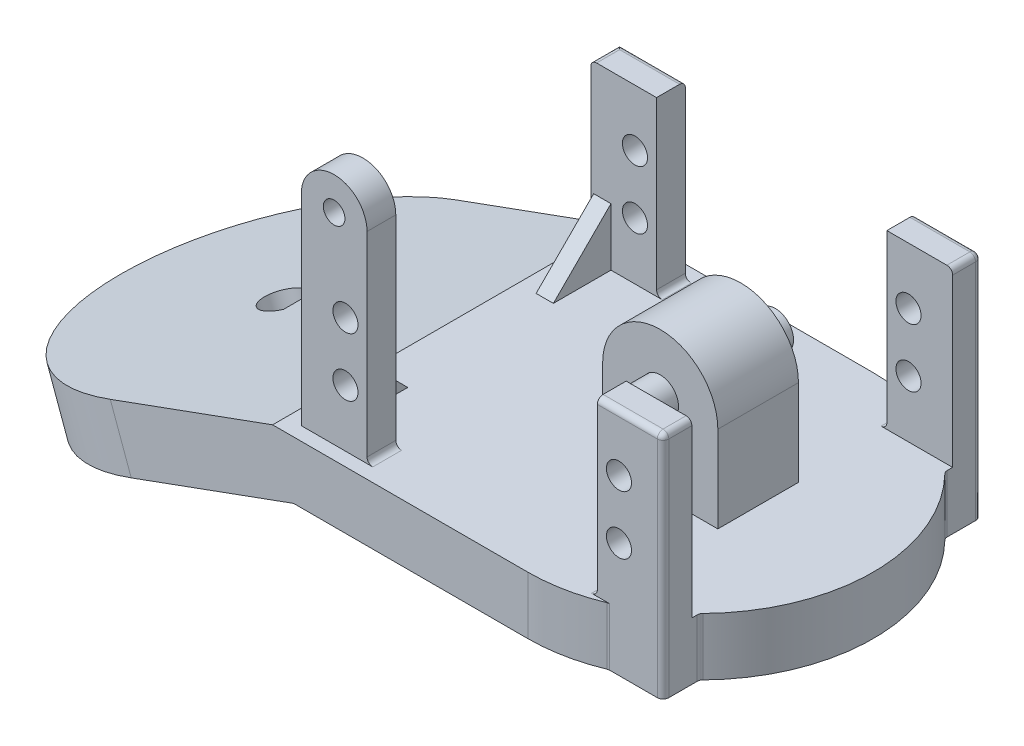
SolidWorks part; units mm, degrees
ref_plane "Plan de face" through (0, 0, 0) normal (0, 0, 1) x (1, 0, 0)
ref_plane "Plan de dessus" through (0, 0, 0) normal (0, 1, 0) x (1, 0, 0)
ref_plane "Plan de droite" through (0, 0, 0) normal (1, 0, 0) x (0, 0, -1)
sketch "Esquisse5" plane through (0, 0, 0) normal (0, 1, 0) x (1, 0, 0)
  line L0 (42.5, 0) -> (-42.5, 0) construction
  line L1 (42.5, -30) -> (-42.5, -30)
  line L2 (42.5, 30) -> (-42.5, 30)
  arc A0 (42.5, -30) -> (42.5, 30) centre (42.5, 0) ccw
  arc A1 (-42.5, 30) -> (-42.5, -30) centre (-42.5, 0) ccw
  point P2 (0, 0)
  dimension "D2" = 30
  dimension "D1" = 85
extrude "Boss.-Extru.3" add sketch "Esquisse5" along normal mid plane 10
sketch "Esquisse36" plane through (0, 0, 0) normal (0, 0, 1) x (1, 0, 0)
  line L0 (0, 0) -> (9.0993, -25)
  line L1 (9.0993, -25) -> (-112.5, -25)
  line L2 (-112.5, -25) -> (-112.5, 35)
  line L3 (-112.5, 35) -> (-12.739, 35)
  line L4 (-12.739, 35) -> (0, 0)
  line L5 (42.5, -5) -> (-42.5, -5) construction
  line L6 (42.5, 5) -> (-42.5, 5) construction
  line L7 (-42.5, 5) -> (-42.5, -5) construction
  dimension "D1" = 180
  dimension "D2" = 20
  dimension "D3" = 70
  dimension "D4" = 30
  dimension "D5" = 70
sketch "Esquisse7" plane through (0, 0, 0) normal (0, 0, 1) x (1, 0, 0)
  line L0 (42.5, 5) -> (32.5, 5)
  line L1 (-42.5, 5) -> (42.5, 5) construction
  line L2 (32.5, 5) -> (32.5, 20)
  line L3 (32.5, 20) -> (52.5, 20)
  line L4 (52.5, 20) -> (52.5, 5)
  line L5 (72.5, 5) -> (42.5, 5) construction
  line L6 (52.5, 5) -> (42.5, 5)
  arc A0 (32.5, 20) -> (52.5, 20) centre (42.5, 20) cw
  circle A1 centre (42.5, 20) radius 3.175
  dimension "D1" = 10
  dimension "D3" = 6.35
  dimension "D2" = 15
extrude "Boss.-Extru.5" add sketch "Esquisse7" along normal mid plane 14 contours A1 L3 A0 | A1 L3 L2 L0 L6 L4 region at (42.5, 12.1572, 0) region at (42.5, 24.5689, 0)
sketch "Esquisse10" plane through (0, -5, 0) normal (0, -1, 0) x (1, 0, 0)
  point P0 (42.5, 0)
ref_plane "Plan1" through (0, 0, 22.64) normal (0, 0, 1) x (1, 0, 0)
sketch "Esquisse13" plane through (0, 0, 22.64) normal (0, 0, 1) x (1, 0, 0)
  line L0 (-42.5, 5) -> (42.5, 5) construction
  line L1 (5.8, 5) -> (58.63, 5)
  line L2 (5.8, 5) -> (5.8, 29.91) construction
  line L3 (5.8, 29.91) -> (58.63, 29.91) construction
  line L4 (58.63, 5) -> (58.63, 29.91) construction
  line L5 (5.8, 5) -> (0.8, 5)
  line L6 (0.8, 5) -> (0.8, 34.91)
  line L7 (0.8, 34.91) -> (63.63, 34.91)
  line L8 (63.63, 34.91) -> (63.63, 5)
  line L9 (63.63, 5) -> (58.63, 5)
  line L10 (63.63, 5) -> (58.63, 5)
  line L11 (0.8, 5) -> (5.8, 5)
  line L12 (12.215, 5) -> (12.215, 29.91)
  line L13 (12.215, 29.91) -> (52.215, 29.91)
  line L14 (52.215, 29.91) -> (52.215, 5)
  line L15 (52.215, 5) -> (12.215, 5)
  circle A0 centre (42.5, 20) radius 3.175 construction
  circle A2 centre (55.97, 25.08) radius 2.18
  circle A3 centre (55.97, 14.92) radius 2.18
  circle A4 centre (8.47, 25.08) radius 2.18
  circle A5 centre (8.47, 14.92) radius 2.18
  point P6 (58.63, 17.455)
  point P24 (32.215, 29.91)
  point P26 (32.215, 34.91)
  dimension "D4" = 5
  dimension "D7" = 4.36
  dimension "D8" = 47.5
  dimension "D12" = 10.16
  dimension "D1" = 52.83
  dimension "D2" = 16.13
  dimension "D3" = 24.91
  dimension "D5" = 4.83
  dimension "D6" = 2.67
  dimension "D9" = 47.5
  dimension "D10" = 0
  dimension "D11" = 0
  dimension "D13" = 0
  dimension "D14" = 5
  dimension "D15" = 5
  dimension "D16" = 40
  dimension "D17" = 0
  dimension "D18" = 0
extrude "Boss.-Extru.8" add sketch "Esquisse13" along normal blind 5 contours L13 L14 L1 L9 L8 L7 L6 L5 L12 A5 A4 A3 A2 region at (3.3, 5.6959, 22.64)
sketch "Esquisse47" plane through (0, 0, 27.64) normal (0, 0, 1) x (1, 0, 0)
  line L0 (52.215, 29.91) -> (52.215, 5) construction
  line L1 (12.215, 29.91) -> (52.215, 29.91)
  line L2 (12.215, 29.91) -> (12.215, 34.91)
  line L3 (12.215, 34.91) -> (52.215, 34.91)
  line L4 (52.215, 29.91) -> (52.215, 34.91)
  line L5 (12.215, 29.91) -> (52.215, 34.91) construction
  line L6 (12.215, 34.91) -> (52.215, 29.91) construction
  line L7 (12.215, 5) -> (12.215, 29.91) construction
  line L8 (12.215, 29.91) -> (52.215, 29.91) construction
  line L9 (0.8, 34.91) -> (63.63, 34.91) construction
  point P4 (32.215, 32.41)
extrude "Enlèv. mat.-Extru.8" cut sketch "Esquisse47" against normal up to next
ref_plane "Plan12" through (2.8, 0, 0) normal (-1, 0, 0) x (0, 0, 1)
mirror "Symétrie2" about plane through (0, 0, 0) normal (0, 0, 1) of "Enlèv. mat.-Extru.8", "Boss.-Extru.8"
sketch "Esquisse14" plane through (0, 0, 0) normal (0, 0, 1) x (1, 0, 0)
  point P0 (42.5, 20)
sketch "Esquisse33" plane through (0, 5, 0) normal (0, -1, 0) x (1, 0, 0)
  line L0 (54.1632, -27.64) -> (63.63, -27.64) construction
  line L1 (63.63, 27.64) -> (54.1632, 27.64)
  line L2 (63.63, 27.64) -> (63.63, -27.64)
  line L3 (63.63, -27.64) -> (54.1632, -27.64)
  line L4 (54.1632, 27.64) -> (54.1632, -27.64)
  dimension "D1" = 0
  dimension "D2" = 0
extrude "Boss.-Extru.10" add sketch "Esquisse33" along normal up to surface (10 mm away) up to face at (0, -5, 0)
sketch "Esquisse34" plane through (0, 0, 0) normal (0, 1, 0) x (1, 0, 0)
  line L0 (0, 0) -> (0, 29.4868) construction
extrude "Enlèv. mat.-Extru.6" cut sketch "Esquisse36" against normal mid plane 130
ref_plane "Plan11" through (0, 0, 0) normal (-0.342, 0.9397, 0) x (0, 0, -1)
sketch "Esquisse35" plane through (0, 0, 0) normal (-0.342, 0.9397, 0) x (0, 0, -1)
  circle A0 centre (0, 30) radius 30
  dimension "D1" = 60
  dimension "D2" = 0
extrude "Boss.-Extru.11" add sketch "Esquisse35" along normal mid plane 10.64
sketch "Esquisse37" plane through (0, 0, 0) normal (0, 0, 1) x (1, 0, 0)
sketch "Esquisse38" plane through (-1.8195, 4.9992, 0) normal (-0.342, 0.9397, 0) x (0.9397, 0.342, 0)
  point P1 (-30, 0)
sketch "Esquisse39" plane through (1.8195, -4.9992, 0) normal (0.342, -0.9397, 0) x (0.9397, 0.342, 0)
  point P0 (-30, 0)
sketch "Esquisse40" plane through (0, 0, 0) normal (0, 0, 1) x (1, 0, 0)
  line L0 (-26.3712, -15.2598) -> (-30.0103, -5.2614)
  line L1 (-26.3712, -15.2598) -> (1.8195, -4.9992)
  line L2 (-30.0103, -5.2614) -> (-1.8195, 4.9992)
  line L3 (1.8195, -4.9992) -> (-1.8195, 4.9992)
  dimension "D1" = 0
extrude "Boss.-Extru.12" add sketch "Esquisse40" along normal mid plane 60
sketch "Esquisse41" plane through (-1.8195, 4.9992, 0) normal (-0.342, 0.9397, 0) x (0.9397, 0.342, 0)
  line L0 (-27.46, -2.2602) -> (-27.46, 2.2602)
  line L1 (0, -30) -> (0, 30) construction
  arc A1 (-27.46, -2.2602) -> (-27.46, 2.2602) centre (-30, 0) cw
  point P4 (-33.4, 0)
  dimension "D2" = 3.4
  dimension "D3" = 5.94
extrude "Enlèv. mat.-Extru.7" cut sketch "Esquisse41" against normal blind 60
sketch "Esquisse42" plane through (0, 0, 27.64) normal (0, 0, 1) x (1, 0, 0)
  line L0 (0.8, 34.91) -> (0.8, 39.91)
  line L1 (0.8, 39.91) -> (12.215, 39.91)
  line L2 (12.215, 39.91) -> (12.215, 34.91)
  line L3 (0.8, 34.91) -> (12.215, 34.91) construction
  line L4 (12.215, 34.91) -> (0.8, 34.91)
  line L5 (12.215, 5) -> (12.215, 34.91) construction
  arc A0 (0.8, 39.91) -> (12.215, 39.91) centre (6.5075, 39.91) cw
  circle A1 centre (6.5075, 39.91) radius 1.875
  line M15 (63.63, 34.91) -> (52.215, 34.91)
  dimension "D3" = 3.75
  dimension "D1" = 5
  dimension "D2" = 0
extrude "Boss.-Extru.13" add sketch "Esquisse42" against normal up to surface (5 mm away) contours A1 L1 A0 | A1 L1 L0 L2 M15 region at (6.5075, 37.2274, 27.64) region at (6.5075, 42.5291, 27.64) up to face at (10.65, 25.08, 22.64)
sketch "Esquisse45" plane through (2.8, 0, 0) normal (-1, 0, 0) x (0, 0, 1)
  line L0 (22.64, 14.9996) -> (12.64, 4.9996)
  line L1 (22.64, 5) -> (22.64, 39.91) construction
  line L2 (30, 4.9996) -> (-30, 4.9996) construction
  dimension "D1" = 10
  dimension "D2" = 10
rib "Nervure4" sketch "Esquisse45" sketch "Esquisse45" thickness 3 extrusion direction parallel to sketch draft on no parameters "D1"=3
fillet "Congé1" radius 1 6 edges at (54.1632, 0, 27.64) (63.63, 14.955, 27.64) (63.63, 0, 21.2961) (54.1632, 0, -27.64) (63.63, 0, -21.2961) (63.63, 14.955, -27.64)
mirror "Symétrie3" about plane through (0, 0, 0) normal (0, 0, 1) of "Nervure4"
fillet "Congé2" radius 1 11 edges at (6.5075, 34.91, -27.64) (63.3371, 34.91, -27.3471) (57.4225, 34.91, 27.64) (63.3371, 34.91, 27.3471) (63.63, 34.91, -24.64) (0.8, 34.91, -25.14) (52.215, 5, -25.14) (12.215, 5, -25.14) (12.215, 5, 25.14) (52.215, 5, 25.14) (63.63, 34.91, 24.64)
sketch "Esquisse48" plane through (0, 0, 0) normal (0, 0, 1) x (1, 0, 0)
  circle A0 centre (42.5, 20) radius 3.15
  dimension "D1" = 6.3
extrude "Boss.-Extru.14" add sketch "Esquisse48" along normal blind 13 and the other way blind 13
